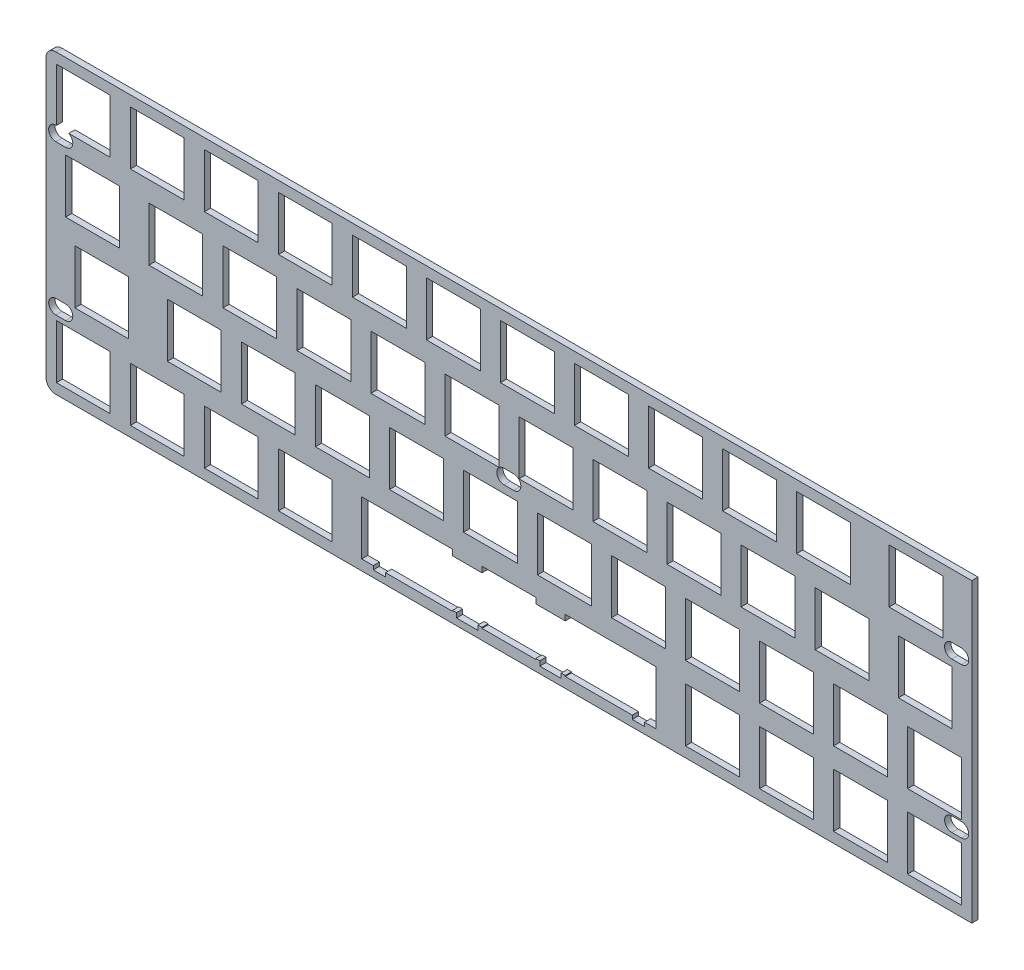
SolidWorks part; units mm, degrees
ref_plane "Front Plane" through (0, 0, 0) normal (0, 0, 1) x (1, 0, 0)
ref_plane "Top Plane" through (0, 0, 0) normal (0, 1, 0) x (1, 0, 0)
ref_plane "Right Plane" through (0, 0, 0) normal (1, 0, 0) x (0, 0, -1)
sketch "Model" plane through (0, 0, 0) normal (0, 0, 1) x (1, 0, 0)
  line L0 (0.0951, 76.4575) -> (238.37, 76.4575)
  line L1 (238.37, 76.4575) -> (238.37, 0.1075)
  line L2 (238.37, 0.1075) -> (0.0951, 0.1075)
  line L3 (0.0951, 0.1075) -> (0.0951, 76.4575)
  line L4 (81.3513, 16.6329) -> (81.3513, 2.7836)
  line L5 (81.3513, 2.7836) -> (84.3248, 2.7836)
  line L6 (84.3248, 2.7836) -> (84.3248, 1.8135)
  line L7 (84.3248, 1.8135) -> (87.4751, 1.8135)
  line L8 (87.4751, 1.8135) -> (87.4751, 2.7836)
  line L9 (87.4751, 2.7836) -> (104.725, 2.7836)
  line L10 (104.725, 2.7836) -> (104.725, 3.0138)
  line L11 (104.725, 3.0138) -> (105.756, 3.0138)
  line L12 (105.756, 3.0138) -> (105.756, 1.8135)
  line L13 (105.756, 1.8135) -> (111.275, 1.8135)
  line L14 (111.275, 1.8135) -> (111.275, 3.0138)
  line L15 (111.275, 3.0138) -> (112.306, 3.0138)
  line L16 (112.306, 3.0138) -> (112.306, 2.7836)
  line L17 (112.306, 2.7836) -> (126.157, 2.7836)
  line L18 (126.157, 2.7836) -> (126.157, 3.0138)
  line L19 (126.157, 3.0138) -> (127.187, 3.0138)
  line L20 (127.187, 3.0138) -> (127.187, 1.8135)
  line L21 (127.187, 1.8135) -> (132.707, 1.8135)
  line L22 (132.707, 1.8135) -> (132.707, 3.0138)
  line L23 (132.707, 3.0138) -> (133.737, 3.0138)
  line L24 (133.737, 3.0138) -> (133.737, 2.7836)
  line L25 (133.737, 2.7836) -> (150.987, 2.7836)
  line L26 (150.987, 2.7836) -> (150.987, 1.8135)
  line L27 (150.987, 1.8135) -> (154.138, 1.8135)
  line L28 (154.138, 1.8135) -> (154.138, 2.7836)
  line L29 (154.138, 2.7836) -> (157.113, 2.7836)
  line L30 (157.113, 2.7836) -> (157.113, 16.6329)
  line L31 (157.113, 16.6329) -> (133.737, 16.6329)
  line L32 (133.737, 16.6329) -> (133.737, 15.1639)
  line L33 (133.737, 15.1639) -> (126.157, 15.1639)
  line L34 (126.157, 15.1639) -> (126.157, 16.6329)
  line L35 (126.157, 16.6329) -> (112.306, 16.6329)
  line L36 (112.306, 16.6329) -> (112.306, 15.1639)
  line L37 (112.306, 15.1639) -> (104.725, 15.1639)
  line L38 (104.725, 15.1639) -> (104.725, 16.6329)
  line L39 (104.725, 16.6329) -> (81.3513, 16.6329)
  line L40 (221.845, 16.6329) -> (235.694, 16.6329)
  line L41 (235.694, 16.6329) -> (235.694, 2.7836)
  line L42 (235.694, 2.7836) -> (221.845, 2.7836)
  line L43 (221.845, 2.7836) -> (221.845, 16.6329)
  line L44 (202.795, 16.6329) -> (216.644, 16.6329)
  line L45 (216.644, 16.6329) -> (216.644, 2.7836)
  line L46 (216.644, 2.7836) -> (202.795, 2.7836)
  line L47 (202.795, 2.7836) -> (202.795, 16.6329)
  line L48 (183.745, 16.6329) -> (197.594, 16.6329)
  line L49 (197.594, 16.6329) -> (197.594, 2.7836)
  line L50 (197.594, 2.7836) -> (183.745, 2.7836)
  line L51 (183.745, 2.7836) -> (183.745, 16.6329)
  line L52 (164.695, 16.6329) -> (178.544, 16.6329)
  line L53 (178.544, 16.6329) -> (178.544, 2.7836)
  line L54 (178.544, 2.7836) -> (164.695, 2.7836)
  line L55 (164.695, 2.7836) -> (164.695, 16.6329)
  line L56 (59.92, 16.6329) -> (73.769, 16.6329)
  line L57 (73.769, 16.6329) -> (73.769, 2.7836)
  line L58 (73.769, 2.7836) -> (59.92, 2.7836)
  line L59 (59.92, 2.7836) -> (59.92, 16.6329)
  line L60 (40.87, 16.6329) -> (54.719, 16.6329)
  line L61 (54.719, 16.6329) -> (54.719, 2.7836)
  line L62 (54.719, 2.7836) -> (40.87, 2.7836)
  line L63 (40.87, 2.7836) -> (40.87, 16.6329)
  line L64 (21.8199, 16.6329) -> (35.669, 16.6329)
  line L65 (35.669, 16.6329) -> (35.669, 2.7836)
  line L66 (35.669, 2.7836) -> (21.8199, 2.7836)
  line L67 (21.8199, 2.7836) -> (21.8199, 16.6329)
  line L68 (2.7699, 16.6329) -> (16.6192, 16.6329)
  line L69 (16.6192, 16.6329) -> (16.6192, 2.7836)
  line L70 (16.6192, 2.7836) -> (2.7699, 2.7836)
  line L71 (2.7699, 2.7836) -> (2.7699, 16.6329)
  line L72 (221.845, 35.6828) -> (235.694, 35.6828)
  line L73 (235.694, 35.6828) -> (235.694, 21.8336)
  line L74 (235.694, 21.8336) -> (221.845, 21.8336)
  line L75 (221.845, 21.8336) -> (221.845, 35.6828)
  line L76 (202.795, 35.6828) -> (216.644, 35.6828)
  line L77 (216.644, 35.6828) -> (216.644, 21.8336)
  line L78 (216.644, 21.8336) -> (202.795, 21.8336)
  line L79 (202.795, 21.8336) -> (202.795, 35.6828)
  line L80 (183.745, 35.6828) -> (197.594, 35.6828)
  line L81 (197.594, 35.6828) -> (197.594, 21.8336)
  line L82 (197.594, 21.8336) -> (183.745, 21.8336)
  line L83 (183.745, 21.8336) -> (183.745, 35.6828)
  line L84 (164.695, 35.6828) -> (178.544, 35.6828)
  line L85 (178.544, 35.6828) -> (178.544, 21.8336)
  line L86 (178.544, 21.8336) -> (164.695, 21.8336)
  line L87 (164.695, 21.8336) -> (164.695, 35.6828)
  line L88 (145.644, 35.6828) -> (159.494, 35.6828)
  line L89 (159.494, 35.6828) -> (159.494, 21.8336)
  line L90 (159.494, 21.8336) -> (145.644, 21.8336)
  line L91 (145.644, 21.8336) -> (145.644, 35.6828)
  line L92 (126.594, 35.6828) -> (140.444, 35.6828)
  line L93 (140.444, 35.6828) -> (140.444, 21.8336)
  line L94 (140.444, 21.8336) -> (126.594, 21.8336)
  line L95 (126.594, 21.8336) -> (126.594, 35.6828)
  line L96 (107.544, 35.6828) -> (121.394, 35.6828)
  line L97 (121.394, 35.6828) -> (121.394, 21.8336)
  line L98 (121.394, 21.8336) -> (107.544, 21.8336)
  line L99 (107.544, 21.8336) -> (107.544, 35.6828)
  line L100 (88.4936, 35.6828) -> (102.344, 35.6828)
  line L101 (102.344, 35.6828) -> (102.344, 21.8336)
  line L102 (102.344, 21.8336) -> (88.4936, 21.8336)
  line L103 (88.4936, 21.8336) -> (88.4936, 35.6828)
  line L104 (69.445, 35.6828) -> (83.294, 35.6828)
  line L105 (83.294, 35.6828) -> (83.294, 21.8336)
  line L106 (83.294, 21.8336) -> (69.445, 21.8336)
  line L107 (69.445, 21.8336) -> (69.445, 35.6828)
  line L108 (50.395, 35.6828) -> (64.244, 35.6828)
  line L109 (64.244, 35.6828) -> (64.244, 21.8336)
  line L110 (64.244, 21.8336) -> (50.395, 21.8336)
  line L111 (50.395, 21.8336) -> (50.395, 35.6828)
  line L112 (31.3449, 35.6828) -> (45.194, 35.6828)
  line L113 (45.194, 35.6828) -> (45.194, 21.8336)
  line L114 (45.194, 21.8336) -> (31.3449, 21.8336)
  line L115 (31.3449, 21.8336) -> (31.3449, 35.6828)
  line L116 (7.531, 35.6828) -> (21.3817, 35.6828)
  line L117 (21.3817, 35.6828) -> (21.3817, 21.8336)
  line L118 (21.3817, 21.8336) -> (7.531, 21.8336)
  line L119 (7.531, 21.8336) -> (7.531, 35.6828)
  line L120 (219.462, 54.7328) -> (233.313, 54.7328)
  line L121 (233.313, 54.7328) -> (233.313, 40.8838)
  line L122 (233.313, 40.8838) -> (219.462, 40.8838)
  line L123 (219.462, 40.8838) -> (219.462, 54.7328)
  line L124 (198.031, 54.7328) -> (211.882, 54.7328)
  line L125 (211.882, 54.7328) -> (211.882, 40.8838)
  line L126 (211.882, 40.8838) -> (198.031, 40.8838)
  line L127 (198.031, 40.8838) -> (198.031, 54.7328)
  line L128 (178.981, 54.7328) -> (192.832, 54.7328)
  line L129 (192.832, 54.7328) -> (192.832, 40.8838)
  line L130 (192.832, 40.8838) -> (178.981, 40.8838)
  line L131 (178.981, 40.8838) -> (178.981, 54.7328)
  line L132 (159.931, 54.7328) -> (173.782, 54.7328)
  line L133 (173.782, 54.7328) -> (173.782, 40.8838)
  line L134 (173.782, 40.8838) -> (159.931, 40.8838)
  line L135 (159.931, 40.8838) -> (159.931, 54.7328)
  line L136 (140.881, 54.7328) -> (154.732, 54.7328)
  line L137 (154.732, 54.7328) -> (154.732, 40.8838)
  line L138 (154.732, 40.8838) -> (140.881, 40.8838)
  line L139 (140.881, 40.8838) -> (140.881, 54.7328)
  line L140 (121.831, 54.7328) -> (135.682, 54.7328)
  line L141 (135.682, 54.7328) -> (135.682, 40.8838)
  line L142 (135.682, 40.8838) -> (121.831, 40.8838)
  line L143 (121.831, 40.8838) -> (121.831, 54.7328)
  line L144 (102.781, 54.7328) -> (116.632, 54.7328)
  line L145 (116.632, 54.7328) -> (116.632, 40.8838)
  line L146 (116.632, 40.8838) -> (102.781, 40.8838)
  line L147 (102.781, 40.8838) -> (102.781, 54.7328)
  line L148 (83.7311, 54.7328) -> (97.5815, 54.7328)
  line L149 (97.5815, 54.7328) -> (97.5815, 40.8838)
  line L150 (97.5815, 40.8838) -> (83.7311, 40.8838)
  line L151 (83.7311, 40.8838) -> (83.7311, 54.7328)
  line L152 (64.6811, 54.7328) -> (78.5315, 54.7328)
  line L153 (78.5315, 54.7328) -> (78.5315, 40.8838)
  line L154 (78.5315, 40.8838) -> (64.6811, 40.8838)
  line L155 (64.6811, 40.8838) -> (64.6811, 54.7328)
  line L156 (45.6311, 54.7328) -> (59.4815, 54.7328)
  line L157 (59.4815, 54.7328) -> (59.4815, 40.8838)
  line L158 (59.4815, 40.8838) -> (45.6311, 40.8838)
  line L159 (45.6311, 40.8838) -> (45.6311, 54.7328)
  line L160 (26.581, 54.7328) -> (40.4315, 54.7328)
  line L161 (40.4315, 54.7328) -> (40.4315, 40.8838)
  line L162 (40.4315, 40.8838) -> (26.581, 40.8838)
  line L163 (26.581, 40.8838) -> (26.581, 54.7328)
  line L164 (5.1511, 54.7328) -> (19.0004, 54.7328)
  line L165 (19.0004, 54.7328) -> (19.0004, 40.8838)
  line L166 (19.0004, 40.8838) -> (5.1511, 40.8838)
  line L167 (5.1511, 40.8838) -> (5.1511, 54.7328)
  line L168 (217.081, 73.7828) -> (230.932, 73.7828)
  line L169 (230.932, 73.7828) -> (230.932, 59.9338)
  line L170 (230.932, 59.9338) -> (217.081, 59.9338)
  line L171 (217.081, 59.9338) -> (217.081, 73.7828)
  line L172 (193.27, 73.7828) -> (207.119, 73.7828)
  line L173 (207.119, 73.7828) -> (207.119, 59.9338)
  line L174 (207.119, 59.9338) -> (193.27, 59.9338)
  line L175 (193.27, 59.9338) -> (193.27, 73.7828)
  line L176 (174.22, 73.7828) -> (188.069, 73.7828)
  line L177 (188.069, 73.7828) -> (188.069, 59.9338)
  line L178 (188.069, 59.9338) -> (174.22, 59.9338)
  line L179 (174.22, 59.9338) -> (174.22, 73.7828)
  line L180 (155.17, 73.7828) -> (169.019, 73.7828)
  line L181 (169.019, 73.7828) -> (169.019, 59.9338)
  line L182 (169.019, 59.9338) -> (155.17, 59.9338)
  line L183 (155.17, 59.9338) -> (155.17, 73.7828)
  line L184 (136.12, 73.7828) -> (149.969, 73.7828)
  line L185 (149.969, 73.7828) -> (149.969, 59.9338)
  line L186 (149.969, 59.9338) -> (136.12, 59.9338)
  line L187 (136.12, 59.9338) -> (136.12, 73.7828)
  line L188 (117.07, 73.7828) -> (130.919, 73.7828)
  line L189 (130.919, 73.7828) -> (130.919, 59.9338)
  line L190 (130.919, 59.9338) -> (117.07, 59.9338)
  line L191 (117.07, 59.9338) -> (117.07, 73.7828)
  line L192 (98.02, 73.7828) -> (111.869, 73.7828)
  line L193 (111.869, 73.7828) -> (111.869, 59.9338)
  line L194 (111.869, 59.9338) -> (98.02, 59.9338)
  line L195 (98.02, 59.9338) -> (98.02, 73.7828)
  line L196 (78.97, 73.7828) -> (92.819, 73.7828)
  line L197 (92.819, 73.7828) -> (92.819, 59.9338)
  line L198 (92.819, 59.9338) -> (78.97, 59.9338)
  line L199 (78.97, 59.9338) -> (78.97, 73.7828)
  line L200 (59.92, 73.7828) -> (73.769, 73.7828)
  line L201 (73.769, 73.7828) -> (73.769, 59.9338)
  line L202 (73.769, 59.9338) -> (59.92, 59.9338)
  line L203 (59.92, 59.9338) -> (59.92, 73.7828)
  line L204 (40.87, 73.7828) -> (54.719, 73.7828)
  line L205 (54.719, 73.7828) -> (54.719, 59.9338)
  line L206 (54.719, 59.9338) -> (40.87, 59.9338)
  line L207 (40.87, 59.9338) -> (40.87, 73.7828)
  line L208 (21.8199, 73.7828) -> (35.669, 73.7828)
  line L209 (35.669, 73.7828) -> (35.669, 59.9338)
  line L210 (35.669, 59.9338) -> (21.8199, 59.9338)
  line L211 (21.8199, 59.9338) -> (21.8199, 73.7828)
  line L212 (2.7699, 73.7828) -> (16.6192, 73.7828)
  line L213 (16.6192, 73.7828) -> (16.6192, 59.9338)
  line L214 (16.6192, 59.9338) -> (2.7699, 59.9338)
  line L215 (2.7699, 59.9338) -> (2.7699, 73.7828)
extrude "Boss-Extrude1" add sketch "Model" along normal blind 1.6
fillet "Fillet1" radius 2.5 2 edges at (0.0951, 0.1075, 0.8) (0.0951, 76.4575, 0.8)
sketch "Sketch10" plane through (0, 0, 1.6) normal (0, 0, 1) x (1, 0, 0)
  line L0 (233.2257, 20.8643) -> (235.7275, 20.8468) construction
  line L1 (235.71, 18.3475) -> (233.2287, 18.3649) construction
  line L2 (2.5951, 0.1075) -> (238.37, 0.1075) construction
  line L3 (238.37, 0.1075) -> (238.37, 76.4575) construction
  line L4 (235.71, 57.0181) -> (233.2081, 57.0181) construction
  line L5 (233.2081, 59.5175) -> (235.71, 59.5175) construction
  line L6 (238.37, 76.4575) -> (2.5951, 76.4575) construction
  line L7 (120.46, 38.2181) -> (117.9581, 38.2181) construction
  line L8 (117.9581, 40.7175) -> (120.46, 40.7175) construction
  line L9 (5.137, 57.0181) -> (2.6351, 57.0181) construction
  line L10 (2.6351, 59.5175) -> (5.137, 59.5175) construction
  line L11 (5.137, 18.4075) -> (2.6351, 18.4075) construction
  line L12 (2.6351, 20.9068) -> (5.137, 20.9068) construction
  line L13 (5.137, 56.4181) -> (2.6351, 56.4181)
  line L14 (0.0951, 73.9575) -> (0.0951, 2.6075) construction
  line L15 (2.6351, 60.1175) -> (5.137, 60.1175)
  line L16 (2.6351, 21.5068) -> (5.137, 21.5068)
  line L17 (5.137, 17.8075) -> (2.6351, 17.8075)
  line L18 (120.46, 37.6181) -> (117.9581, 37.6181)
  line L19 (117.9581, 41.3175) -> (120.46, 41.3175)
  line L20 (235.71, 56.4181) -> (233.2081, 56.4181)
  line L21 (233.2081, 60.1175) -> (235.71, 60.1175)
  line L22 (235.7058, 17.7475) -> (233.2267, 17.7649)
  line L23 (233.2277, 21.4643) -> (235.7317, 21.4468)
  arc A0 (235.71, 18.3475) -> (235.7275, 20.8468) centre (235.7188, 19.5971) ccw construction
  arc A1 (233.2257, 20.8643) -> (233.2287, 18.3649) centre (233.2272, 19.6146) ccw construction
  arc A2 (235.71, 57.0181) -> (235.71, 59.5175) centre (235.71, 58.2678) ccw construction
  arc A3 (233.2081, 59.5175) -> (233.2081, 57.0181) centre (233.2081, 58.2678) ccw construction
  arc A4 (120.46, 38.2181) -> (120.46, 40.7175) centre (120.46, 39.4678) ccw construction
  arc A5 (117.9581, 40.7175) -> (117.9581, 38.2181) centre (117.9581, 39.4678) ccw construction
  arc A6 (5.137, 57.0181) -> (5.137, 59.5175) centre (5.137, 58.2678) ccw construction
  arc A7 (2.6351, 59.5175) -> (2.6351, 57.0181) centre (2.6351, 58.2678) ccw construction
  arc A8 (5.137, 18.4075) -> (5.137, 20.9068) centre (5.137, 19.6572) ccw construction
  arc A9 (2.6351, 20.9068) -> (2.6351, 18.4075) centre (2.6351, 19.6572) ccw construction
  arc A10 (2.6351, 60.1175) -> (2.6351, 56.4181) centre (2.6351, 58.2678) ccw
  arc A11 (5.137, 56.4181) -> (5.137, 60.1175) centre (5.137, 58.2678) ccw
  arc A12 (5.137, 17.8075) -> (5.137, 21.5068) centre (5.137, 19.6572) ccw
  arc A13 (2.6351, 21.5068) -> (2.6351, 17.8075) centre (2.6351, 19.6572) ccw
  arc A14 (117.9581, 41.3175) -> (117.9581, 37.6181) centre (117.9581, 39.4678) ccw
  arc A15 (120.46, 37.6181) -> (120.46, 41.3175) centre (120.46, 39.4678) ccw
  arc A16 (233.2081, 60.1175) -> (233.2081, 56.4181) centre (233.2081, 58.2678) ccw
  arc A17 (235.71, 56.4181) -> (235.71, 60.1175) centre (235.71, 58.2678) ccw
  arc A18 (233.2277, 21.4643) -> (233.2267, 17.7649) centre (233.2272, 19.6146) ccw
  arc A19 (235.7058, 17.7475) -> (235.7317, 21.4468) centre (235.7188, 19.5971) ccw
  dimension "D13" = 1.2497
  dimension "D14" = 1.2497
  dimension "D1" = 2.5019
  dimension "D2" = 1.2497
  dimension "D3" = 1.2497
  dimension "D4" = 2.4994
  dimension "D5" = 18.24
  dimension "D6" = 2.66
  dimension "D7" = 1.2497
  dimension "D8" = 1.2497
  dimension "D9" = 2.5019
  dimension "D10" = 2.4994
  dimension "D11" = 16.94
  dimension "D12" = 2.66
  dimension "D15" = 117.91
  dimension "D16" = 35.74
  dimension "D17" = 18.3
  dimension "D18" = 2.54
  dimension "D19" = 16.94
  dimension "D20" = 2.54
  dimension "D21" = 0.6
extrude "Cut-Extrude1" cut sketch "Sketch10" against normal blind 1.6
